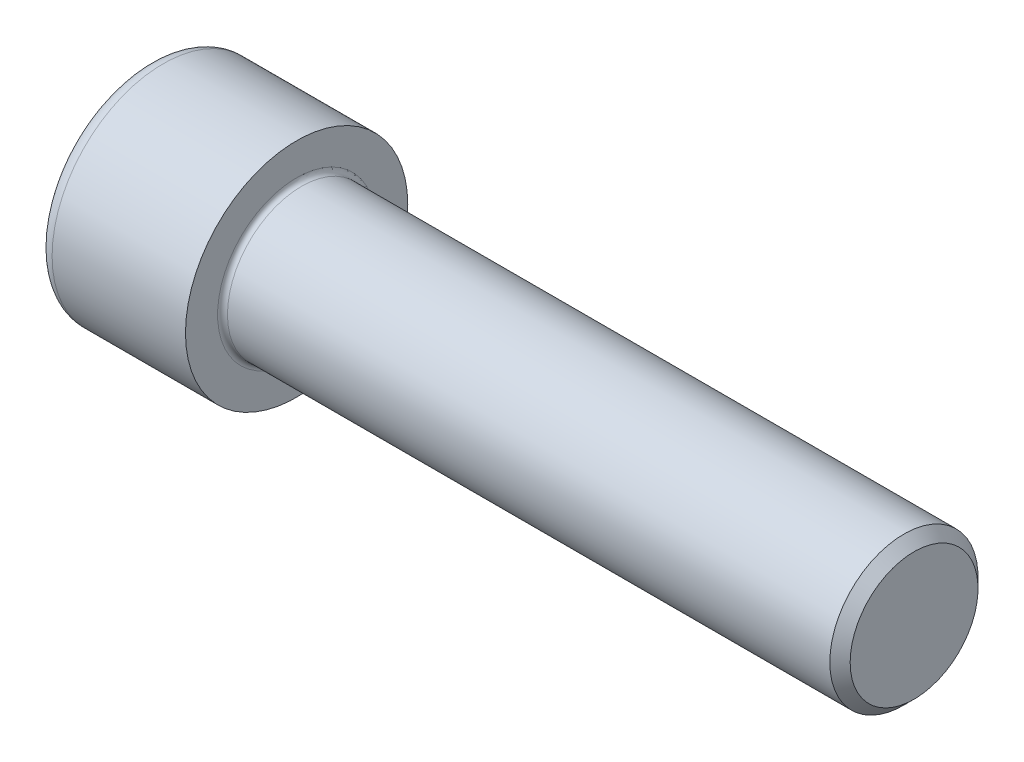
SolidWorks part; units mm, degrees
ref_plane "Front Plane" through (0, 0, 0) normal (0, 0, 1) x (1, 0, 0)
ref_plane "Top Plane" through (0, 0, 0) normal (0, 1, 0) x (1, 0, 0)
ref_plane "Right Plane" through (0, 0, 0) normal (1, 0, 0) x (0, 0, -1)
sketch "BaseHeadSke" plane through (0, 0, 0) normal (1, 0, 0) x (0, 0, -1)
  circle A1 centre (0, 0) radius 18
  dimension "Head_diameter" = 36
extrude "BaseHead" add sketch "BaseHeadSke" along normal blind 24
sketch "BodySke" plane through (0, 0, 0) normal (0, 0, 1) x (1, 0, 0)
  line L0 (0, 0) -> (124, 0)
  line L1 (124, 0) -> (124, 10.352)
  line L2 (124, 10.352) -> (122.352, 12)
  line L3 (122.352, 12) -> (0, 12)
  line L4 (0, 12) -> (0, 0)
  line L6 (0, 0) -> (159.3976, 0) construction
  line L7 (64, -84.3176) -> (64, 77.7215) construction
  line L8 (121, -21.5941) -> (121, 39.2994) construction
  line L10 (24, -18) -> (24, 18) construction
  dimension "Length" = 100
  dimension "Thread_length" = 60
  dimension "Advance" = 3
revolve "BaseBody" add sketch "BodySke" angle 360 about L6
cosmetic thread "ThreadCosmetic" [suppressed] parameters "Thread_length"=60, "Thread_minor"=20.704
sketch "CutSocketSke" plane through (0, 0, 0) normal (1, 0, 0) x (0, 0, -1)
  line L1 (0, 10.9697) -> (-9.5, 5.4848)
  line L2 (-9.5, 5.4848) -> (-9.5, -5.4848)
  line L3 (-9.5, -5.4848) -> (0, -10.9697)
  line L4 (0, -10.9697) -> (9.5, -5.4848)
  line L5 (9.5, -5.4848) -> (9.5, 5.4848)
  line L6 (9.5, 5.4848) -> (0, 10.9697)
  circle A0 centre (0, 0) radius 9.5 construction
extrude "CutSocket" cut sketch "CutSocketSke" along normal blind 12
sketch "CutHoleSke" plane through (0, 0, 0) normal (0, 0, 1) x (1, 0, 0)
  line L0 (0, 0) -> (149.4323, 0) construction
  line L1 (0, 9.5) -> (13.6, 9.5)
  line L2 (13.6, 9.5) -> (19.0848, 0)
  line L3 (19.0848, 0) -> (0, 0)
  line L4 (0, 0) -> (0, 9.5)
  line L6 (24, -18) -> (24, 18) construction
  dimension "D1" = 60
  dimension "Hole_depth" = 10.4
  dimension "D2" = 19
revolve "CutHole" cut sketch "CutHoleSke" angle 360 about L0
fillet "Fillet1" radius 0.8 1 edges at (24, 0, -12)
fillet "Fillet2" radius 2.4 1 edges at (0, 0, -18)
sketch "ThdSchSke" plane through (0, 0, 0) normal (0, 0, 1) x (1, 0, 0)
  line L0 (120.0485, 13.9029) -> (120.0485, 12)
  line L1 (120.0485, 12) -> (121, 10.352)
  line L2 (121, 10.352) -> (121.9515, 12)
  line L3 (121.9515, 12) -> (121.9515, 13.9029)
  line L4 (121.9515, 13.9029) -> (120.0485, 13.9029)
  line L6 (0, 0) -> (141.9934, 0) construction
  line L7 (124, -10.352) -> (124, 10.352) construction
  dimension "D2" = 20.704
  dimension "D3" = 24
  dimension "Advance" = 3
revolve "ThreadSchematic" [suppressed] cut sketch "ThdSchSke" angle 360 about L6
pattern_linear "ThdSchPat" [suppressed] count 19 spacing 3 along (-1, 0, 0) of bodies 107
equation "\"Thread_minor@ThreadCosmetic\" = \"Minor_dia@BodySke\""
equation "\"Thread_length@ThreadCosmetic\" = \"Thread_length@BodySke\""
equation "\"D2@CutHoleSke\" = \"Socket_width@CutSocketSke\""
equation "\"D2@ThdSchSke\" = \"Minor_dia@BodySke\""
equation "\"D3@ThdSchSke\" = \"Diameter@BodySke\""
equation "\"Advance@ThdSchSke\" = \"Advance@BodySke\""
equation "\"D3@ThdSchPat\" = \"Advance@BodySke\""
equation "\"D1@ThdSchPat\" =  int( \"Thread_length@BodySke\"/\"Advance@BodySke\" )-1"
